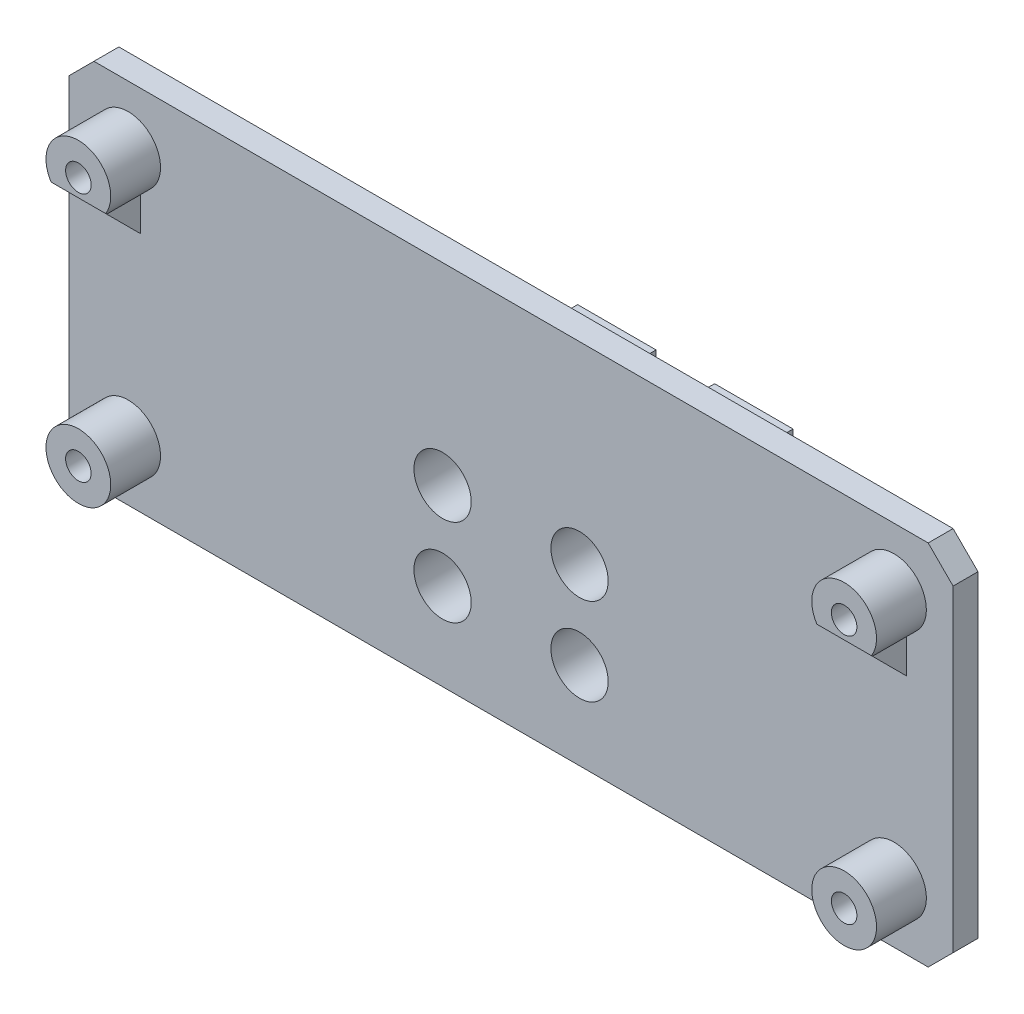
SolidWorks part; units mm, degrees
ref_plane "Front Plane" through (0, 0, 0) normal (0, 0, 1) x (1, 0, 0)
ref_plane "Top Plane" through (0, 0, 0) normal (0, 1, 0) x (1, 0, 0)
ref_plane "Right Plane" through (0, 0, 0) normal (1, 0, 0) x (0, 0, -1)
sketch "Sketch1" plane through (0, 0, 0) normal (0, 0, 1) x (1, 0, 0)
  line L0 (-33.5, 14.75) -> (-35.5, 12.75)
  line L1 (33.5, -14.75) -> (-33.5, -14.75)
  line L2 (35.5, -12.75) -> (35.5, 12.75)
  line L3 (33.5, 14.75) -> (-33.5, 14.75)
  line L4 (-35.5, -12.75) -> (-35.5, 12.75)
  line L5 (35.5, -14.75) -> (-35.5, 14.75) construction
  line L6 (35.5, 14.75) -> (-35.5, -14.75) construction
  line L7 (-33.5, -14.75) -> (-35.5, -12.75)
  line L8 (35.5, -12.75) -> (33.5, -14.75)
  line L9 (35.5, 12.75) -> (33.5, 14.75)
  line L10 (0, 0) -> (0, 9.4643) construction
  line L11 (0, 0) -> (-10.7143, 0) construction
  circle A0 centre (-30.75, 10.03) radius 1.025 construction
  point P0 (0, 0)
  dimension "D3" = 2.05
  dimension "D1" = 71
  dimension "D2" = 29.5
  dimension "D4" = 30.75
  dimension "D5" = 10.03
extrude "Boss-Extrude1" add sketch "Sketch1" along normal blind 2
sketch "Sketch5" plane through (0, 0, 2) normal (0, 0, 1) x (1, 0, 0)
  line L0 (0, 0) -> (0, 9.4643) construction
  line L1 (0, 0) -> (0, 9.4643) construction
  line L2 (0, 0) -> (-10.7143, 0) construction
  line L3 (0, 0) -> (-10.7143, 0) construction
  circle A0 centre (-30.75, 10.03) radius 1.025 construction
  circle A1 centre (-30.75, 10.03) radius 1.025 construction
  circle A2 centre (-30.75, 10.03) radius 2.6
  circle A3 centre (30.75, 10.03) radius 1.025 construction
  circle A4 centre (30.75, 10.03) radius 2.6
  circle A5 centre (30.75, -10.03) radius 1.025 construction
  circle A6 centre (-30.75, -10.03) radius 1.025 construction
  circle A7 centre (30.75, -10.03) radius 2.6
  circle A8 centre (-30.75, -10.03) radius 2.6
  dimension "D1" = 5.2
extrude "Boss-Extrude4" add sketch "Sketch5" along normal blind 4
sketch "Sketch6" plane through (0, 0, 6) normal (0, 0, 1) x (1, 0, 0)
  line L0 (-8.8836, 0) -> (0, 0) construction
  line L1 (0, 0) -> (0, 10.0703) construction
  circle A0 centre (-30.75, 10.03) radius 1.025 construction
  circle A1 centre (-30.75, 10.03) radius 1.025
  circle A2 centre (30.75, 10.03) radius 1.025
  circle A3 centre (30.75, -10.03) radius 1.025
  circle A4 centre (-30.75, -10.03) radius 1.025
extrude "Cut-Extrude1" cut sketch "Sketch6" against normal through all
sketch "Sketch7" plane through (0, 0, 2) normal (0, 0, 1) x (1, 0, 0)
  line L0 (4.5306, 0) -> (0, 0) construction
  line L5 (0, 0) -> (0, 8.7934) construction
  line L7 (-31.75, 7.63) -> (-31.75, 3.63)
  line L8 (-31.75, 3.63) -> (-29.75, 3.63)
  line L9 (-29.75, 7.63) -> (-29.75, 3.63)
  line L10 (-30.75, 7.43) -> (-29.75, 3.63) construction
  line L11 (-31.75, 3.63) -> (-30.75, 7.43) construction
  line L12 (31.75, 3.63) -> (30.75, 7.43) construction
  line L13 (30.75, 7.43) -> (29.75, 3.63) construction
  line L14 (29.75, 7.63) -> (29.75, 3.63)
  line L15 (31.75, 3.63) -> (29.75, 3.63)
  line L16 (31.75, 7.63) -> (31.75, 3.63)
  arc A0 (31.75, 7.63) -> (29.75, 7.63) centre (30.75, 10.03) cw
  circle A1 centre (-30.75, 10.03) radius 2.6 construction
  circle A2 centre (-30.75, 10.03) radius 2.6 construction
  arc A3 (-31.75, 7.63) -> (-29.75, 7.63) centre (-30.75, 10.03) ccw
  point P9 (-30.75, 7.43)
  dimension "D1" = 4
  dimension "D2" = 2
extrude "Boss-Extrude6" add sketch "Sketch7" along normal blind 4
chamfer "Chamfer1" distance 5 angle 45 2 edges at (-30.75, 3.63, 6) (30.75, 3.63, 6)
sketch "Sketch8" plane through (0, 0, 0) normal (0, 0, -1) x (-1, 0, 0)
  line L0 (33.5, -14.75) -> (-33.5, -14.75) construction
  line L1 (-2.35, -14.75) -> (-8.65, -14.75)
  line L2 (-2.35, -14.75) -> (-2.35, 3.25)
  line L3 (-2.35, 3.25) -> (-8.65, 3.25)
  line L4 (-8.65, -14.75) -> (-8.65, 3.25)
  line L5 (-5.5, -0.75) -> (-5.5, -14.75) construction
  line L6 (0, 0) -> (0, -14.75) construction
  line L7 (5.5, -0.75) -> (5.5, -14.75) construction
  line L8 (8.65, -14.75) -> (8.65, 3.25)
  line L9 (2.35, 3.25) -> (8.65, 3.25)
  line L10 (2.35, -14.75) -> (2.35, 3.25)
  line L11 (2.35, -14.75) -> (8.65, -14.75)
  circle A0 centre (-5.5, -0.75) radius 1.05 construction
  circle A1 centre (-5.5, -7.75) radius 1.05 construction
  circle A2 centre (-5.5, -0.75) radius 2.3 construction
  circle A3 centre (-5.5, -7.75) radius 2.3 construction
  circle A4 centre (5.5, -7.75) radius 2.3 construction
  circle A5 centre (5.5, -0.75) radius 2.3 construction
  circle A6 centre (5.5, -7.75) radius 1.05 construction
  circle A7 centre (5.5, -0.75) radius 1.05 construction
  dimension "D3" = 2.1
  dimension "D4" = 4.6
  dimension "D1" = 14
  dimension "D2" = 7
  dimension "D5" = 6.3
  dimension "D6" = 18
  dimension "D7" = 5.5
extrude "Boss-Extrude8" add sketch "Sketch8" along normal blind 12
sketch "Sketch9" plane through (0, 0, 2) normal (0, 0, 1) x (1, 0, 0)
  line L0 (0, 0) -> (0, -14.75) construction
  line L1 (-33.5, -14.75) -> (33.5, -14.75) construction
  circle A0 centre (5.5, -7.75) radius 1.05 construction
  circle A1 centre (5.5, -0.75) radius 1.05 construction
  circle A2 centre (5.5, -7.75) radius 1.05
  circle A3 centre (5.5, -0.75) radius 1.05
  circle A4 centre (-5.5, -0.75) radius 1.05
  circle A5 centre (-5.5, -7.75) radius 1.05
extrude "Cut-Extrude3" cut sketch "Sketch9" against normal through all
sketch "Sketch10" plane through (0, 0, 2) normal (0, 0, 1) x (1, 0, 0)
  line L0 (0, 0) -> (0, -14.75) construction
  line L1 (-33.5, -14.75) -> (33.5, -14.75) construction
  circle A0 centre (5.5, -7.75) radius 2.3 construction
  circle A1 centre (5.5, -0.75) radius 2.3 construction
  circle A2 centre (5.5, -7.75) radius 2.3
  circle A3 centre (5.5, -0.75) radius 2.3
  circle A4 centre (-5.5, -0.75) radius 2.3
  circle A5 centre (-5.5, -7.75) radius 2.3
extrude "Cut-Extrude4" cut sketch "Sketch10" against normal offset from surface (12.5 mm away) 1.5 up to face at (6.55, -0.75, -12)
